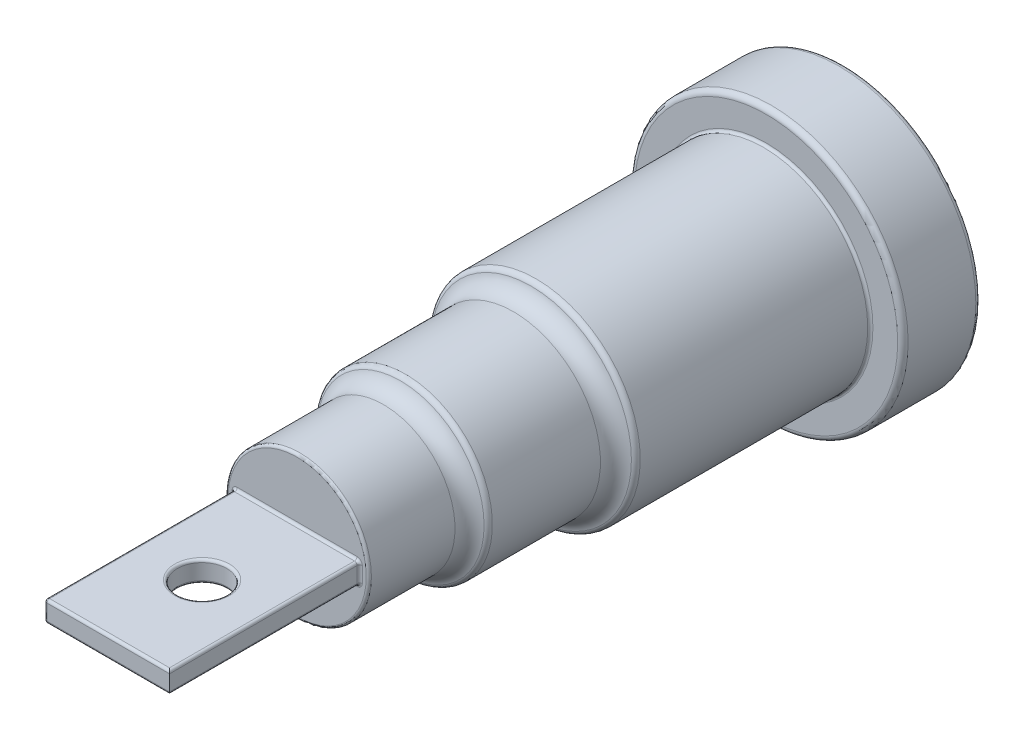
SolidWorks part; units mm, degrees
material "Custom Plastic"
ref_plane "X-Y Datum" through (0, 0, 0) normal (0, 0, 1) x (1, 0, 0)
ref_plane "X-Z Datum" through (0, 0, 0) normal (0, 1, 0) x (1, 0, 0)
ref_plane "Y-Z Datum" through (0, 0, 0) normal (1, 0, 0) x (0, 0, -1)
sketch "Sketch2" plane through (0, 0, 0) normal (0, 0, 1) x (1, 0, 0)
  circle A0 centre (0, 0) radius 5.25
  dimension "D1" = 10.5
extrude "Boss-Extrude1" add sketch "Sketch2" along normal blind 3
sketch "Sketch3" plane through (0, 0, 3) normal (0, 0, 1) x (1, 0, 0)
  circle A0 centre (0, 0) radius 4
  dimension "D1" = 8
extrude "Boss-Extrude2" add sketch "Sketch3" along normal blind 9
sketch "Sketch4" plane through (0, 0, 12) normal (0, 0, 1) x (1, 0, 0)
  circle A0 centre (0, 0) radius 3.34
  dimension "D1" = 6.68
extrude "Boss-Extrude3" add sketch "Sketch4" along normal blind 5
sketch "Sketch5" plane through (0, 0, 17) normal (0, 0, 1) x (1, 0, 0)
  circle A0 centre (0, 0) radius 2.75
  dimension "D1" = 5.5
extrude "Boss-Extrude4" add sketch "Sketch5" along normal blind 4
sketch "Sketch6" plane through (0, 0, 21) normal (0, 0, 1) x (1, 0, 0)
  line L1 (-2.4, 0.4) -> (2.4, 0.4)
  line L2 (-2.4, 0.4) -> (-2.4, -0.4)
  line L3 (-2.4, -0.4) -> (2.4, -0.4)
  line L4 (2.4, 0.4) -> (2.4, -0.4)
  line L5 (-2.4, 0.4) -> (2.4, -0.4) construction
  line L6 (-2.4, -0.4) -> (2.4, 0.4) construction
  point P0 (0, 0)
  dimension "D1" = 0.8
  dimension "D2" = 4.8
extrude "Boss-Extrude5" add sketch "Sketch6" along normal blind 7.3
sketch "Sketch7" plane through (0, -0.4, 0) normal (0, -1, 0) x (1, 0, 0)
  line L0 (0, 21) -> (0, 28.3) construction
  line L1 (2.75, 21) -> (-2.75, 21) construction
  line L2 (-2.4, 28.3) -> (2.4, 28.3) construction
  circle A0 centre (0, 24.65) radius 0.95
  dimension "D1" = 1.9
extrude "Cut-Extrude1" cut sketch "Sketch7" against normal through all
sketch "Sketch8" plane through (0, 0, 0) normal (0, 0, -1) x (-1, 0, 0)
  circle A0 centre (0, 0) radius 2.5
  dimension "D1" = 5
extrude "Cut-Extrude2" cut sketch "Sketch8" against normal blind 15
fillet "Fillet1" radius 0.1 14 edges at (2.75, 0, 21) (2.4, 0, 21) (2.4, 0.4, 24.65) (0, 0.4, 28.3) (0, 0.4, 21) (0, 0.4, 23.7) (-2.4, 0.4, 24.65) (-2.4, 0, 28.3) (-2.4, 0, 21) (-2.4, -0.4, 24.65) (0, -0.4, 28.3) (2.4, -0.4, 24.65) (0, -0.4, 21) (0, -0.4, 23.7)
fillet "Fillet2" radius 0.1 1 edges at (4, 0, 3)
fillet "Fillet3" radius 0.7 2 edges at (2.75, 0, 17) (3.34, 0, 12)
fillet "Fillet5" radius 0.2 2 edges at (3.34, 0, 17) (4, 0, 12)
fillet "Fillet6" radius 0.2 2 edges at (5.25, 0, 3) (5.25, 0, 0)
chamfer "Chamfer1" distance 1 angle 45 1 edges at (-2.5, 0, 0)
